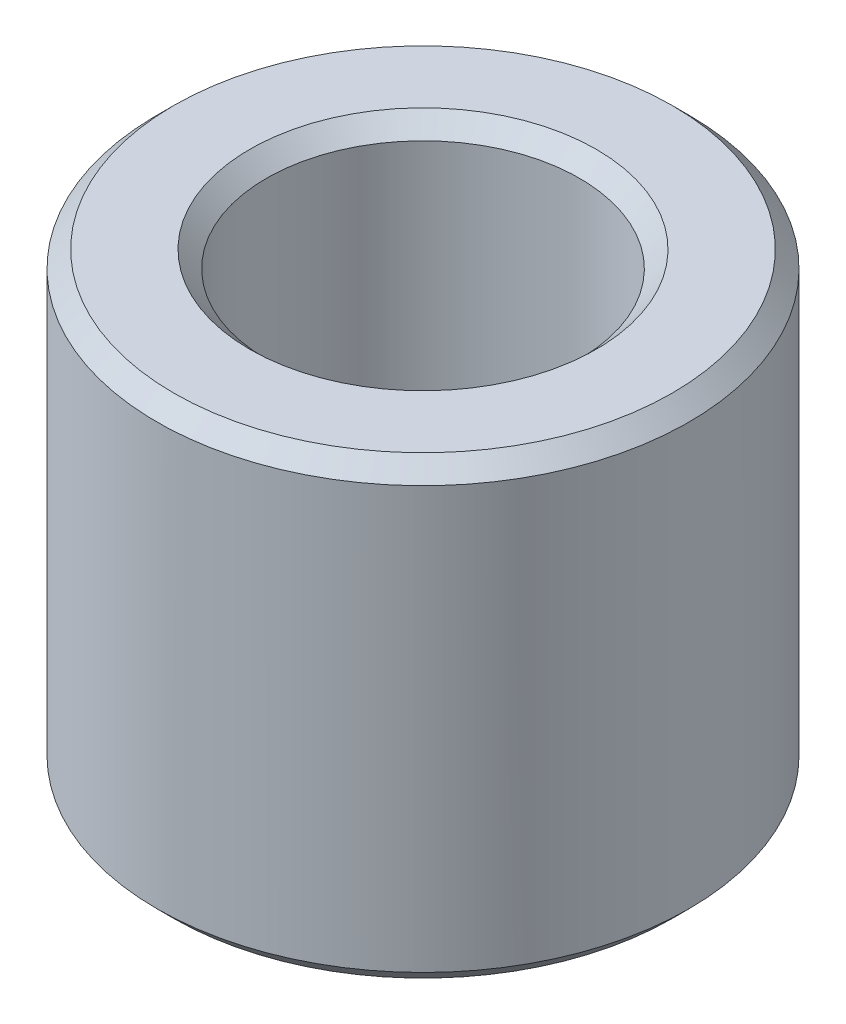
SolidWorks part; units mm, degrees
ref_plane "Front Plane" through (0, 0, 0) normal (0, 0, 1) x (1, 0, 0)
ref_plane "Top Plane" through (0, 0, 0) normal (0, 1, 0) x (1, 0, 0)
ref_plane "Right Plane" through (0, 0, 0) normal (1, 0, 0) x (0, 0, -1)
sketch "Sketch1" plane through (0, 0, 0) normal (0, 1, 0) x (1, 0, 0)
  circle A0 centre (0, 0) radius 7.5
  dimension "SLEEVE_OD" = 15
extrude "Boss-Extrude1" add sketch "Sketch1" along normal blind 12.8342
sketch "Sketch2" plane through (0, 0, 0) normal (0, 1, 0) x (1, 0, 0)
  circle A0 centre (0, 0) radius 4.4156
  dimension "BORE_D" = 8.8313
extrude "Cut-Extrude1" cut sketch "Sketch2" along normal through all
chamfer "Chamfer1" distance 0.4718 angle 45 4 edges at (0, 12.8342, 4.4156) (0, 0, 4.4156) (0, 0, 7.5) (0, 12.8342, 7.5)
